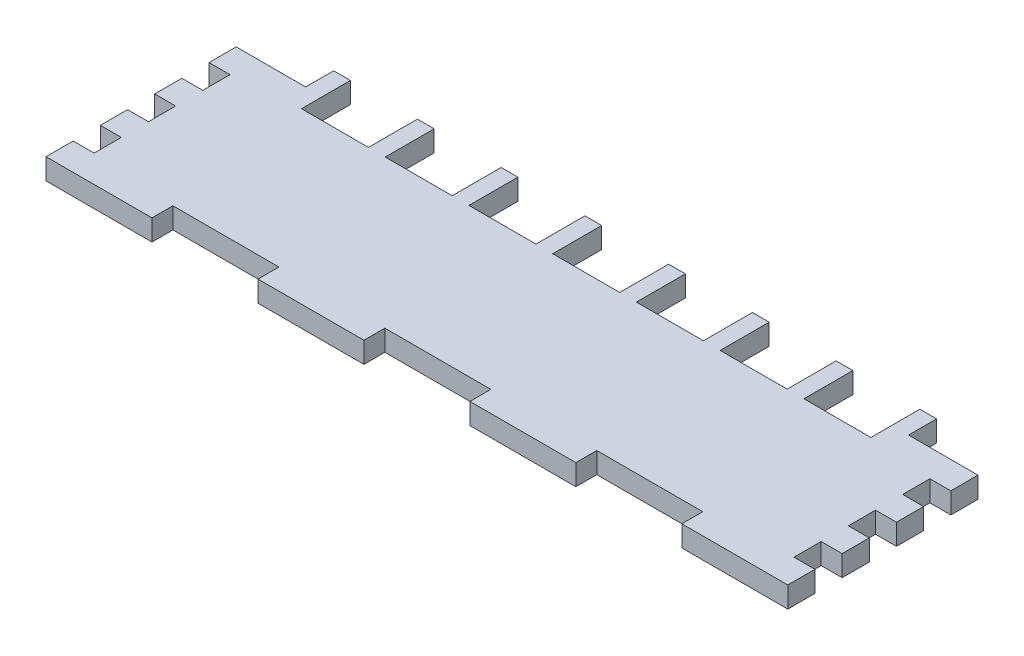
SolidWorks part; units mm, degrees
ref_plane "Front Plane" through (0, 0, 0) normal (0, 0, 1) x (1, 0, 0)
ref_plane "Top Plane" through (0, 0, 0) normal (0, 1, 0) x (1, 0, 0)
ref_plane "Right Plane" through (0, 0, 0) normal (1, 0, 0) x (0, 0, -1)
sketch "Sketch1" plane through (0, 0, 0) normal (0, 1, 0) x (1, 0, 0)
  line L48 (32.1429, 0) -> (32.1429, 6.35)
  line L49 (0, 0) -> (32.1429, 0)
  line L50 (0, 0) -> (0, 6.35)
  line L51 (0, 6.35) -> (32.1429, 6.35)
  line L52 (32.1429, 0) -> (32.1429, 6.35)
  line L53 (0, 0) -> (6.35, 0)
  line L54 (0, 0) -> (0, 8.2429)
  line L55 (0, 8.2429) -> (6.35, 8.2429)
  line L56 (6.35, 0) -> (6.35, 8.2429)
  line L57 (32.1429, 0) -> (64.2857, 0)
  line L58 (64.2857, 0) -> (64.2857, 6.35)
  line L59 (32.1429, 6.35) -> (64.2857, 6.35)
  line L60 (64.2857, 0) -> (64.2857, 6.35)
  line L61 (64.2857, 0) -> (96.4286, 0)
  line L62 (96.4286, 0) -> (96.4286, 6.35)
  line L63 (64.2857, 6.35) -> (96.4286, 6.35)
  line L64 (96.4286, 0) -> (96.4286, 6.35)
  line L65 (96.4286, 0) -> (128.5714, 0)
  line L66 (128.5714, 0) -> (128.5714, 6.35)
  line L67 (96.4286, 6.35) -> (128.5714, 6.35)
  line L72 (128.5714, 0) -> (128.5714, 6.35)
  line L73 (128.5714, 0) -> (160.7143, 0)
  line L74 (160.7143, 0) -> (160.7143, 6.35)
  line L75 (128.5714, 6.35) -> (160.7143, 6.35)
  line L76 (160.7143, 0) -> (160.7143, 6.35)
  line L77 (160.7143, 0) -> (192.8571, 0)
  line L78 (192.8571, 0) -> (192.8571, 6.35)
  line L79 (160.7143, 6.35) -> (192.8571, 6.35)
  line L80 (192.8571, 0) -> (192.8571, 6.35)
  line L81 (192.8571, 0) -> (225, 0)
  line L82 (225, 0) -> (225, 6.35)
  line L83 (192.8571, 6.35) -> (225, 6.35)
  line L84 (0, 8.2429) -> (0, 16.4857)
  line L85 (0, 8.2429) -> (6.35, 8.2429)
  line L86 (6.35, 8.2429) -> (6.35, 16.4857)
  line L87 (0, 16.4857) -> (6.35, 16.4857)
  line L88 (0, 16.4857) -> (0, 24.7286)
  line L89 (0, 16.4857) -> (6.35, 16.4857)
  line L90 (6.35, 16.4857) -> (6.35, 24.7286)
  line L91 (0, 24.7286) -> (6.35, 24.7286)
  line L98 (0, 24.7286) -> (0, 32.9714)
  line L99 (0, 24.7286) -> (6.35, 24.7286)
  line L100 (6.35, 24.7286) -> (6.35, 32.9714)
  line L101 (0, 32.9714) -> (6.35, 32.9714)
  line L102 (0, 32.9714) -> (0, 41.2143)
  line L103 (0, 32.9714) -> (6.35, 32.9714)
  line L104 (6.35, 32.9714) -> (6.35, 41.2143)
  line L105 (0, 41.2143) -> (6.35, 41.2143)
  line L106 (0, 41.2143) -> (0, 49.4571)
  line L107 (0, 41.2143) -> (6.35, 41.2143)
  line L108 (6.35, 41.2143) -> (6.35, 49.4571)
  line L109 (0, 49.4571) -> (6.35, 49.4571)
  line L110 (0, 49.4571) -> (0, 57.7)
  line L111 (0, 49.4571) -> (6.35, 49.4571)
  line L112 (6.35, 49.4571) -> (6.35, 57.7)
  line L113 (0, 57.7) -> (6.35, 57.7)
  line L114 (112.5, 0) -> (112.5, 671.069) construction
  line L115 (-187.856, 28.85) -> (254.8092, 28.85) construction
  line L116 (225, 8.2429) -> (218.65, 8.2429)
  line L117 (218.65, 0) -> (218.65, 8.2429)
  line L118 (225, 0) -> (218.65, 0)
  line L119 (225, 0) -> (225, 8.2429)
  line L120 (225, 49.4571) -> (218.65, 49.4571)
  line L121 (218.65, 49.4571) -> (218.65, 57.7)
  line L122 (225, 57.7) -> (218.65, 57.7)
  line L123 (225, 49.4571) -> (225, 57.7)
  line L124 (225, 41.2143) -> (218.65, 41.2143)
  line L125 (218.65, 41.2143) -> (218.65, 49.4571)
  line L126 (225, 49.4571) -> (218.65, 49.4571)
  line L127 (225, 41.2143) -> (225, 49.4571)
  line L128 (225, 8.2429) -> (218.65, 8.2429)
  line L129 (218.65, 8.2429) -> (218.65, 16.4857)
  line L130 (225, 16.4857) -> (218.65, 16.4857)
  line L131 (225, 8.2429) -> (225, 16.4857)
  line L132 (225, 32.9714) -> (218.65, 32.9714)
  line L133 (218.65, 32.9714) -> (218.65, 41.2143)
  line L134 (225, 41.2143) -> (218.65, 41.2143)
  line L135 (225, 32.9714) -> (225, 41.2143)
  line L136 (225, 24.7286) -> (218.65, 24.7286)
  line L137 (218.65, 24.7286) -> (218.65, 32.9714)
  line L138 (225, 32.9714) -> (218.65, 32.9714)
  line L139 (225, 24.7286) -> (225, 32.9714)
  line L140 (225, 16.4857) -> (218.65, 16.4857)
  line L141 (218.65, 16.4857) -> (218.65, 24.7286)
  line L142 (225, 24.7286) -> (218.65, 24.7286)
  line L143 (225, 16.4857) -> (225, 24.7286)
  line L144 (192.8571, 57.7) -> (225, 57.7)
  line L145 (225, 57.7) -> (225, 51.35)
  line L146 (192.8571, 51.35) -> (225, 51.35)
  line L147 (192.8571, 57.7) -> (192.8571, 51.35)
  line L148 (160.7143, 57.7) -> (192.8571, 57.7)
  line L149 (192.8571, 57.7) -> (192.8571, 51.35)
  line L150 (160.7143, 51.35) -> (192.8571, 51.35)
  line L151 (160.7143, 57.7) -> (160.7143, 51.35)
  line L152 (128.5714, 57.7) -> (160.7143, 57.7)
  line L153 (160.7143, 57.7) -> (160.7143, 51.35)
  line L154 (128.5714, 51.35) -> (160.7143, 51.35)
  line L155 (128.5714, 57.7) -> (128.5714, 51.35)
  line L156 (96.4286, 57.7) -> (128.5714, 57.7)
  line L157 (128.5714, 57.7) -> (128.5714, 51.35)
  line L158 (96.4286, 51.35) -> (128.5714, 51.35)
  line L159 (96.4286, 57.7) -> (96.4286, 51.35)
  line L160 (64.2857, 57.7) -> (96.4286, 57.7)
  line L161 (96.4286, 57.7) -> (96.4286, 51.35)
  line L162 (64.2857, 51.35) -> (96.4286, 51.35)
  line L163 (64.2857, 57.7) -> (64.2857, 51.35)
  line L164 (32.1429, 57.7) -> (64.2857, 57.7)
  line L165 (64.2857, 57.7) -> (64.2857, 51.35)
  line L166 (32.1429, 51.35) -> (64.2857, 51.35)
  line L167 (32.1429, 57.7) -> (32.1429, 51.35)
  line L168 (0, 51.35) -> (32.1429, 51.35)
  line L169 (32.1429, 57.7) -> (32.1429, 51.35)
  line L170 (0, 57.7) -> (32.1429, 57.7)
  line L171 (0, 57.7) -> (0, 51.35)
  point P56 (112.5, 6.35)
  point P58 (6.35, 28.85)
  dimension "D3" = 57.7
  dimension "D4" = 225
  dimension "D5" = 6.35
  dimension "D2" = 7
  dimension "D1" = 7
extrude "Boss-Extrude1" add sketch "Sketch1" along normal blind 6.35 contours L168 L112 L108 L104 L100 L90 L86 L56 L51 L59 L63 L67 L75 L79 L83 L117 L129 L141 L137 L133 L125 L121 L146 L150 L154 L158 L162 L166 | L170 L112 L168 L167 | L160 L163 L162 L159 | L152 L155 L154 L151 | L144 L147 L146 L121 | L121 L146 L123 L122 | L110 L168 L112 L113 | L168 L110 L109 L112 | L51 L56 L55 L54 | L49 L56 L51 L50 | L56 L49 L48 L51 | L63 L58 L61 L62 | L75 L66 L73 L74 | L81 L117 L83 L78 | L117 L81 L82 L83 | L83 L119 L116 L117 | L146 L121 L120 L123 | L132 L135 L124 L133 | L130 L143 L136 L141 | L91 L88 L87 L90 | L105 L102 L101 L104 region at (19.2464, 0, -3.175) region at (112.5, 0, -28.85) region at (3.175, 0, -3.175) region at (80.3571, 0, -3.175) region at (3.175, 0, -7.2964) region at (144.6429, 0, -3.175) region at (3.175, 0, -20.6071) region at (205.7536, 0, -3.175) region at (3.175, 0, -37.0929) region at (221.825, 0, -3.175) region at (221.825, 0, -7.2964) region at (3.175, 0, -50.4036) region at (3.175, 0, -54.525) region at (19.2464, 0, -54.525) region at (221.825, 0, -20.6071) region at (80.3571, 0, -54.525) region at (221.825, 0, -37.0929) region at (144.6429, 0, -54.525) region at (221.825, 0, -50.4036) region at (205.7536, 0, -54.525) region at (221.825, 0, -54.525)
sketch "Sketch2" plane through (0, 6.35, 0) normal (0, 1, 0) x (1, 0, 0)
  line L1 (0, 57.7) -> (225, 57.7)
  line L2 (0, 57.7) -> (0, 49.4571)
  line L3 (0, 49.4571) -> (225, 49.4571)
  line L4 (225, 57.7) -> (225, 49.4571)
extrude "Boss-Extrude2" add sketch "Sketch2" against normal up to surface (6.35 mm away) up to face at (112.5, 0, -28.85)
sketch "Sketch3" plane through (0, 6.35, 0) normal (0, 1, 0) x (1, 0, 0)
  line L0 (0, 57.7) -> (225, 57.7) construction
  line L1 (21.06, 57.7) -> (26.14, 57.7)
  line L2 (21.06, 57.7) -> (21.06, 66.2)
  line L3 (21.06, 66.2) -> (26.14, 66.2)
  line L4 (26.14, 57.7) -> (26.14, 66.2)
  line L5 (46.46, 57.7) -> (46.46, 66.2)
  line L6 (46.46, 57.7) -> (51.54, 57.7)
  line L7 (51.54, 57.7) -> (51.54, 66.2)
  line L8 (46.46, 66.2) -> (51.54, 66.2)
  line L9 (71.86, 57.7) -> (71.86, 66.2)
  line L10 (71.86, 57.7) -> (76.94, 57.7)
  line L11 (76.94, 57.7) -> (76.94, 66.2)
  line L12 (71.86, 66.2) -> (76.94, 66.2)
  line L13 (97.26, 57.7) -> (97.26, 66.2)
  line L14 (97.26, 57.7) -> (102.34, 57.7)
  line L15 (102.34, 57.7) -> (102.34, 66.2)
  line L16 (97.26, 66.2) -> (102.34, 66.2)
  line L17 (122.66, 57.7) -> (122.66, 66.2)
  line L18 (122.66, 57.7) -> (127.74, 57.7)
  line L19 (127.74, 57.7) -> (127.74, 66.2)
  line L20 (122.66, 66.2) -> (127.74, 66.2)
  line L21 (148.06, 57.7) -> (148.06, 66.2)
  line L22 (148.06, 57.7) -> (153.14, 57.7)
  line L23 (153.14, 57.7) -> (153.14, 66.2)
  line L24 (148.06, 66.2) -> (153.14, 66.2)
  line L25 (173.46, 57.7) -> (173.46, 66.2)
  line L26 (173.46, 57.7) -> (178.54, 57.7)
  line L27 (178.54, 57.7) -> (178.54, 66.2)
  line L28 (173.46, 66.2) -> (178.54, 66.2)
  line L29 (198.86, 57.7) -> (198.86, 66.2)
  line L30 (198.86, 57.7) -> (203.94, 57.7)
  line L31 (203.94, 57.7) -> (203.94, 66.2)
  line L32 (198.86, 66.2) -> (203.94, 66.2)
  line L33 (112.5, 6.35) -> (112.5, 90.7817) construction
  line L35 (96.4286, 6.35) -> (128.5714, 6.35) construction
  line L36 (122.66, 66.2) -> (112.5, 66.2) construction
  line L37 (112.5, 66.2) -> (102.34, 66.2) construction
  point P7 (23.6, 66.2)
  point P35 (49, 66.2)
  point P39 (112.5, 6.35)
  dimension "D2" = 25.4
  dimension "D3" = 5.08
  dimension "D4" = 8.5
  dimension "D1" = 8
extrude "Boss-Extrude3" add sketch "Sketch3" against normal up to surface (6.35 mm away) up to face at (112.5, 0, -21.1475)
sketch "Sketch4" plane through (0, 6.35, 0) normal (0, 1, 0) x (1, 0, 0)
  line L0 (71.86, 57.7) -> (71.86, 51.35)
  line L1 (26.14, 57.7) -> (46.46, 57.7)
  line L2 (26.14, 57.7) -> (26.14, 51.35)
  line L3 (26.14, 51.35) -> (46.46, 51.35)
  line L4 (46.46, 57.7) -> (46.46, 51.35)
  line L5 (51.54, 57.7) -> (51.54, 51.35)
  line L6 (51.54, 57.7) -> (71.86, 57.7)
  line L7 (51.54, 51.35) -> (71.86, 51.35)
  line L8 (97.26, 57.7) -> (97.26, 51.35)
  line L9 (76.94, 57.7) -> (76.94, 51.35)
  line L10 (76.94, 57.7) -> (97.26, 57.7)
  line L11 (76.94, 51.35) -> (97.26, 51.35)
  line L12 (122.66, 57.7) -> (122.66, 51.35)
  line L13 (102.34, 57.7) -> (102.34, 51.35)
  line L14 (102.34, 57.7) -> (122.66, 57.7)
  line L15 (102.34, 51.35) -> (122.66, 51.35)
  line L16 (148.06, 57.7) -> (148.06, 51.35)
  line L17 (127.74, 57.7) -> (127.74, 51.35)
  line L18 (127.74, 57.7) -> (148.06, 57.7)
  line L19 (127.74, 51.35) -> (148.06, 51.35)
  line L20 (173.46, 57.7) -> (173.46, 51.35)
  line L21 (153.14, 57.7) -> (153.14, 51.35)
  line L22 (153.14, 57.7) -> (173.46, 57.7)
  line L23 (153.14, 51.35) -> (173.46, 51.35)
  line L24 (198.86, 57.7) -> (198.86, 51.35)
  line L25 (178.54, 57.7) -> (178.54, 51.35)
  line L26 (178.54, 57.7) -> (198.86, 57.7)
  line L27 (178.54, 51.35) -> (198.86, 51.35)
  line L28 (173.46, 66.2) -> (173.46, 57.7) construction
  dimension "D2" = 6.35
  dimension "D1" = 7
extrude "Cut-Extrude1" cut sketch "Sketch4" against normal up to surface (6.35 mm away) up to face at (112.5, 0, -39.2819)
